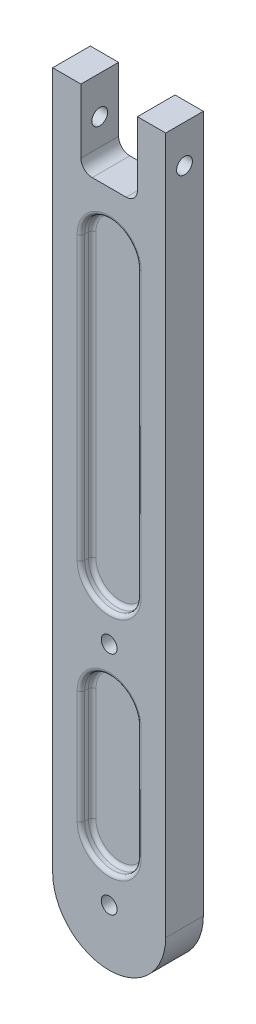
SolidWorks part; units mm, degrees
ref_plane "前视基准面" through (0, 0, 0) normal (0, 0, 1) x (1, 0, 0)
ref_plane "上视基准面" through (0, 0, 0) normal (0, 1, 0) x (1, 0, 0)
ref_plane "右视基准面" through (0, 0, 0) normal (1, 0, 0) x (0, 0, -1)
other "Configuration Table"
sketch "草图1" plane through (0, 0, 0) normal (0, 0, 1) x (1, 0, 0)
  line L1 (0, 0) -> (30, 0)
  line L2 (0, 0) -> (0, 200)
  line L3 (0, 200) -> (30, 200)
  line L4 (30, 0) -> (30, 200)
  dimension "D1" = 30
  dimension "D2" = 200
extrude "凸台-拉伸1" add sketch "草图1" along normal blind 10
fillet "圆角1" 2 edges at (0, 0, 5) (30, 0, 5) type full round first side face at (0, 100, 5) second side face at (30, 100, 5) middle face at (15, 0, 5)
sketch "草图2" plane through (0, 0, 10) normal (0, 0, 1) x (1, 0, 0)
  circle A0 centre (15, 15) radius 2.1
  dimension "D1" = 4.2
extrude "切除-拉伸1" cut sketch "草图2" against normal blind 10
sketch "草图3" plane through (0, 0, 10) normal (0, 0, 1) x (1, 0, 0)
  line L0 (15, 200) -> (15, 0) construction
  line L1 (30, 200) -> (0, 200) construction
  arc A0 (0, 15) -> (30, 15) centre (15, 15) ccw construction
  circle A1 centre (15, 75) radius 2.1
  circle A2 centre (15, 15) radius 2.1 construction
  dimension "D1" = 4.2
  dimension "D2" = 60
extrude "切除-拉伸2" cut sketch "草图3" against normal blind 10
sketch "草图4" plane through (0, 0, 10) normal (0, 0, 1) x (1, 0, 0)
  line L0 (15, 200) -> (15, 0) construction
  line L1 (30, 200) -> (0, 200) construction
  line L3 (7.5, 200) -> (22.5, 200)
  line L4 (7.5, 200) -> (7.5, 180)
  line L5 (7.5, 180) -> (22.5, 180)
  line L6 (22.5, 200) -> (22.5, 180)
  arc A0 (0, 15) -> (30, 15) centre (15, 15) ccw construction
  point P11 (15, 180)
  dimension "D1" = 15
  dimension "D2" = 20
extrude "切除-拉伸3" cut sketch "草图4" against normal blind 10
fillet "圆角4" radius 3 2 edges at (7.5, 180, 5) (22.5, 180, 5)
sketch "草图6" plane through (30, 0, 0) normal (1, 0, 0) x (0, 0, -1)
  line L0 (-5, 200) -> (-5, 0) construction
  line L1 (-10, 200) -> (0, 200) construction
  line L2 (-10, 0) -> (0, 0) construction
  circle A0 centre (-5, 190) radius 2.1
  dimension "D2" = 4.2
  dimension "D1" = 10
extrude "切除-拉伸5" cut sketch "草图6" against normal through all and the other way through all
sketch "草图7" plane through (0, 0, 0) normal (0, 0, -1) x (-1, 0, 0)
  line L0 (-15, 165) -> (-15, 90) construction
  line L1 (-10.5, 180) -> (-19.5, 180) construction
  line L2 (-15, 0) -> (-15, 180) construction
  line L3 (-7.5, 165) -> (-7.5, 90)
  line L4 (-22.5, 165) -> (-22.5, 90)
  line L5 (-15, 60) -> (-15, 30) construction
  line L6 (-7.5, 60) -> (-7.5, 30)
  line L7 (-22.5, 60) -> (-22.5, 30)
  arc A0 (-30, 15) -> (0, 15) centre (-15, 15) ccw construction
  arc A1 (-7.5, 165) -> (-22.5, 165) centre (-15, 165) ccw
  arc A2 (-22.5, 90) -> (-7.5, 90) centre (-15, 90) ccw
  circle A3 centre (-15, 75) radius 2.1 construction
  arc A4 (-7.5, 60) -> (-22.5, 60) centre (-15, 60) ccw
  arc A5 (-22.5, 30) -> (-7.5, 30) centre (-15, 30) ccw
  circle A6 centre (-15, 15) radius 2.1 construction
  point P5 (-15, 127.5)
  point P18 (-15, 45)
  dimension "D2" = 15
  dimension "D3" = 15
  dimension "D5" = 15
  dimension "D6" = 15
  dimension "D1" = 15
  dimension "D4" = 15
extrude "切除-拉伸6" cut sketch "草图7" against normal blind 3
fillet "圆角5" radius 1 16 edges at (15, 172.5, 0) (7.5, 127.5, 0) (15, 82.5, 0) (15, 67.5, 0) (7.5, 45, 0) (15, 22.5, 0) (7.5, 45, 3) (15, 22.5, 3) (22.5, 45, 3) (15, 67.5, 3) (7.5, 127.5, 3) (15, 82.5, 3) (22.5, 127.5, 3) (15, 172.5, 3) (22.5, 127.5, 0) (22.5, 45, 0)
sketch "草图8" plane through (0, 0, 10) normal (0, 0, 1) x (1, 0, 0)
  line L0 (15, 180) -> (15, 0) construction
  line L1 (10.5, 180) -> (19.5, 180) construction
  line L2 (15, 165) -> (15, 90) construction
  line L3 (22.5, 165) -> (22.5, 90)
  line L4 (7.5, 165) -> (7.5, 90)
  line L5 (15, 60) -> (15, 30) construction
  line L6 (22.5, 60) -> (22.5, 30)
  line L7 (7.5, 60) -> (7.5, 30)
  arc A0 (0, 15) -> (30, 15) centre (15, 15) ccw construction
  arc A1 (22.5, 165) -> (7.5, 165) centre (15, 165) ccw
  arc A2 (7.5, 90) -> (22.5, 90) centre (15, 90) ccw
  arc A3 (22.5, 60) -> (7.5, 60) centre (15, 60) ccw
  arc A4 (7.5, 30) -> (22.5, 30) centre (15, 30) ccw
  circle A5 centre (15, 75) radius 2.1 construction
  circle A6 centre (15, 15) radius 2.1 construction
  point P9 (15, 127.5)
  point P16 (15, 45)
  dimension "D3" = 15
  dimension "D4" = 15
  dimension "D5" = 15
  dimension "D6" = 15
  dimension "D1" = 15
  dimension "D2" = 15
extrude "切除-拉伸7" cut sketch "草图8" against normal blind 3
fillet "圆角6" radius 1 16 edges at (15, 172.5, 10) (22.5, 127.5, 10) (15, 82.5, 10) (15, 67.5, 10) (22.5, 45, 10) (15, 22.5, 10) (22.5, 45, 7) (15, 22.5, 7) (7.5, 45, 7) (15, 67.5, 7) (22.5, 127.5, 7) (15, 82.5, 7) (7.5, 127.5, 7) (15, 172.5, 7) (7.5, 127.5, 10) (7.5, 45, 10)
